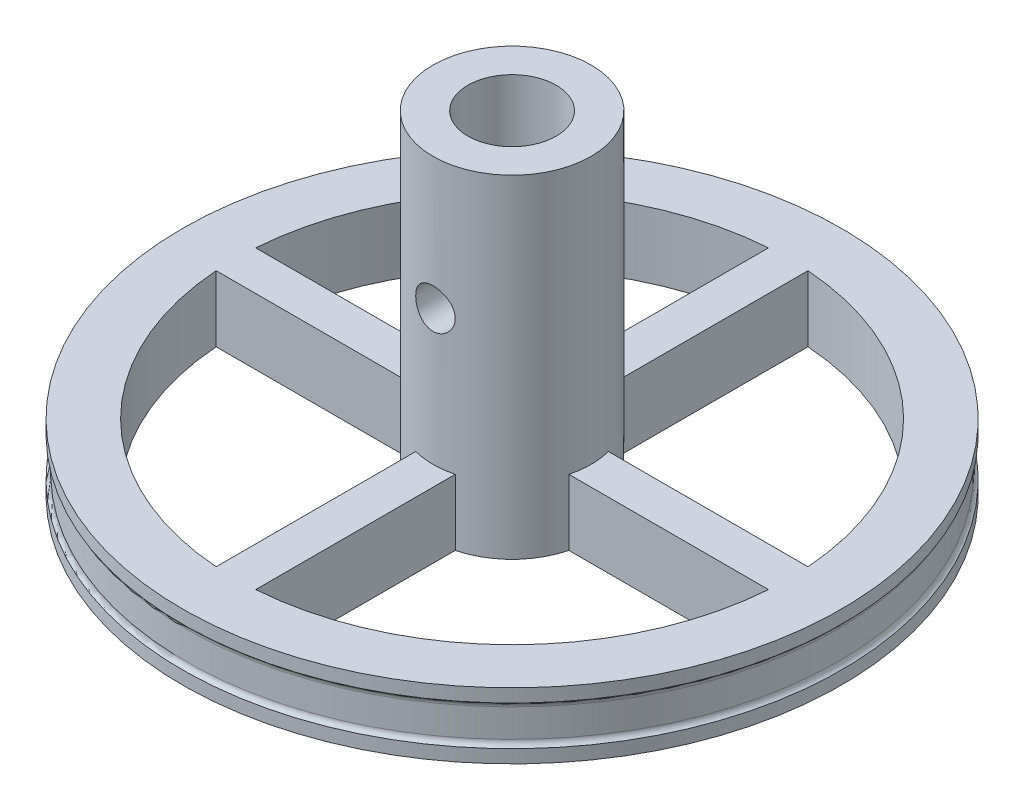
SolidWorks part; units mm, degrees
ref_plane "Front Plane" through (0, 0, 0) normal (0, 0, 1) x (1, 0, 0)
ref_plane "Top Plane" through (0, 0, 0) normal (0, 1, 0) x (1, 0, 0)
ref_plane "Right Plane" through (0, 0, 0) normal (1, 0, 0) x (0, 0, -1)
sketch "Sketch1" plane through (0, 0, 0) normal (0, 0, 1) x (1, 0, 0)
  line L0 (0, 2.2639) -> (0, -2.7361)
  line L1 (0, -2.7361) -> (25, -2.7361)
  line L2 (25, -2.7361) -> (25, -1.7361)
  line L3 (25, -1.7361) -> (24.75, -1.7361)
  line L4 (24.75, -1.7361) -> (24.75, 1.2639)
  line L5 (24.75, 1.2639) -> (25, 1.2639)
  line L6 (25, 1.2639) -> (25, 2.2639)
  line L7 (25, 2.2639) -> (0, 2.2639)
  dimension "D1" = 3
  dimension "D2" = 1
  dimension "D3" = 1
  dimension "D4" = 25
  dimension "D6" = 0.25
revolve "Revolve1" add sketch "Sketch1" angle 90 about L0
sketch "Sketch2" plane through (0, 0, 0) normal (0, 1, 0) x (1, 0, 0)
  line L0 (0, -25) -> (0, 0) construction
  line L1 (25, 0) -> (0, 0) construction
  line L2 (0, 0) -> (6, 0)
  line L3 (0, 0) -> (0, -6)
  arc A0 (0, -6) -> (6, 0) centre (0, 0) ccw
  dimension "D1" = 6
extrude "Boss-Extrude2" add sketch "Sketch2" along normal blind 22.5
sketch "Sketch6" plane through (0, 2.2639, 0) normal (0, 1, 0) x (1, 0, 0)
  line L0 (0, -25) -> (0, -6) construction
  line L1 (25, 0) -> (6, 0) construction
  line L2 (1.5, -5.8095) -> (1.5, -20.9464)
  line L3 (5.8095, -1.5) -> (20.9464, -1.5)
  arc A0 (1.5, -5.8095) -> (5.8095, -1.5) centre (0, 0) ccw
  arc A1 (1.5, -20.9464) -> (20.9464, -1.5) centre (0, 0) ccw
  dimension "D1" = 6
  dimension "D2" = 21
  dimension "D3" = 1.5
  dimension "D4" = 1.5
extrude "Cut-Extrude1" cut sketch "Sketch6" against normal through all
mirror "Mirror3" about plane through (0, 0, 0) normal (0, 0, 1) of "Cut-Extrude1", "Boss-Extrude2", "Revolve1"
mirror "Mirror4" about plane through (0, 0, 0) normal (1, 0, 0) of "Cut-Extrude1", "Mirror3", "Boss-Extrude2", "Revolve1"
sketch "Sketch7" plane through (0, 22.5, 0) normal (0, 1, 0) x (1, 0, 0)
  line L0 (0, 5.643) -> (0, -5.8158) construction
  line L1 (-6.3281, 0) -> (5.497, 0) construction
  circle A0 centre (0, 0) radius 3.35
  dimension "D1" = 6.7
extrude "Cut-Extrude2" cut sketch "Sketch7" against normal blind 20
fillet "Fillet9" radius 0.5 2 edges at (-24.75, -1.7361, 0) (-24.75, 1.2639, 0)
sketch "Sketch8" plane through (0, 0, 0) normal (0, 0, 1) x (1, 0, 0)
  line L0 (0, 22.5) -> (0, 0.2722) construction
  line L1 (3.35, 22.5) -> (-3.35, 22.5) construction
  line L2 (6, 22.5) -> (-6, 22.5) construction
  circle A0 centre (0, 12.5) radius 1.5
  dimension "D1" = 3
  dimension "D2" = 10
extrude "Cut-Extrude3" cut sketch "Sketch8" along normal up to next and the other way up to next
